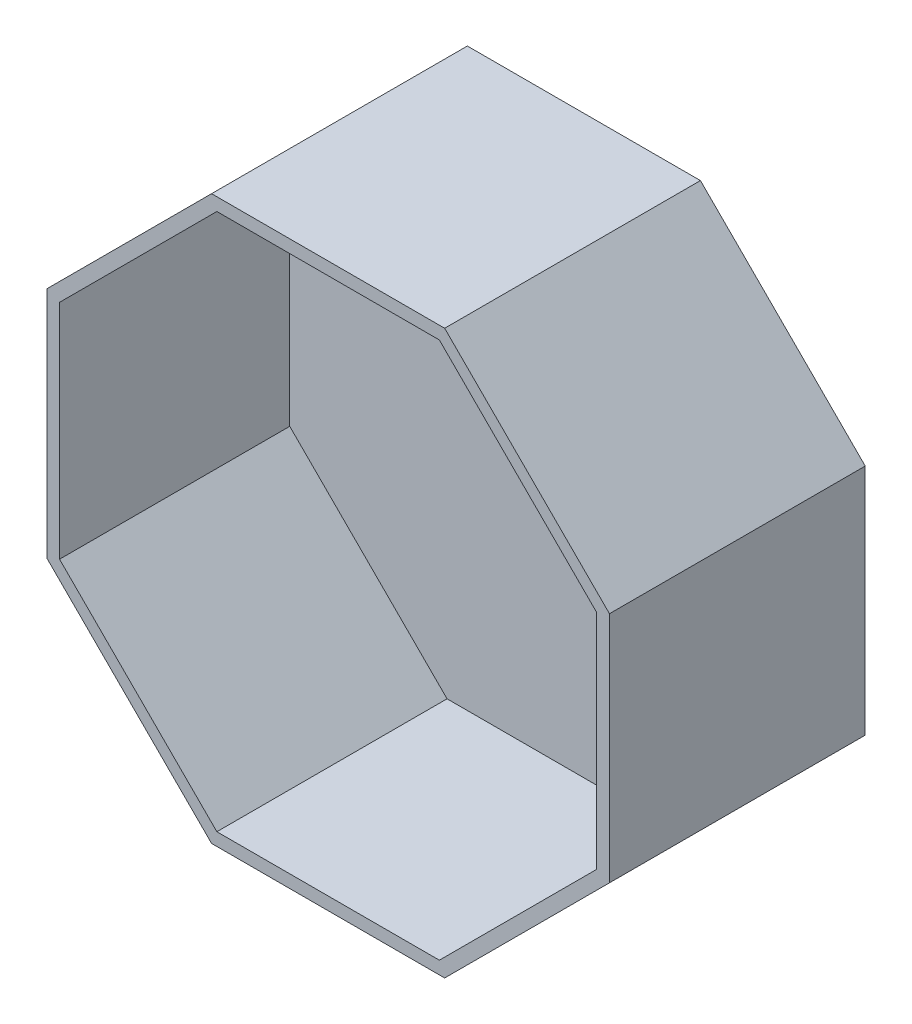
SolidWorks part; units mm, degrees
material "ABS PC"
ref_plane "Front Plane" through (0, 0, 0) normal (0, 0, 1) x (1, 0, 0)
ref_plane "Top Plane" through (0, 0, 0) normal (0, 1, 0) x (1, 0, 0)
ref_plane "Right Plane" through (0, 0, 0) normal (1, 0, 0) x (0, 0, -1)
sketch "Sketch8" plane through (0, 0, 0) normal (0, 0, 1) x (1, 0, 0)
  line L1 (55, 22.7817) -> (22.7817, 55)
  line L2 (22.7817, 55) -> (-22.7817, 55)
  line L3 (-22.7817, 55) -> (-55, 22.7817)
  line L4 (-55, 22.7817) -> (-55, -22.7817)
  line L5 (-55, -22.7817) -> (-22.7817, -55)
  line L6 (-22.7817, -55) -> (22.7817, -55)
  line L7 (22.7817, -55) -> (55, -22.7817)
  line L8 (55, -22.7817) -> (55, 22.7817)
  circle A0 centre (0, 0) radius 55 construction
extrude "Boss-Extrude3" add sketch "Sketch8" along normal blind 50
sketch "Sketch9" plane through (0, 0, 50) normal (0, 0, 1) x (1, 0, 0)
  line L1 (52.5, 21.7462) -> (21.7462, 52.5)
  line L2 (21.7462, 52.5) -> (-21.7462, 52.5)
  line L3 (-21.7462, 52.5) -> (-52.5, 21.7462)
  line L4 (-52.5, 21.7462) -> (-52.5, -21.7462)
  line L5 (-52.5, -21.7462) -> (-21.7462, -52.5)
  line L6 (-21.7462, -52.5) -> (21.7462, -52.5)
  line L7 (21.7462, -52.5) -> (52.5, -21.7462)
  line L8 (52.5, -21.7462) -> (52.5, 21.7462)
  circle A0 centre (0, 0) radius 52.5 construction
extrude "Cut-Extrude3" cut sketch "Sketch9" against normal blind 45
